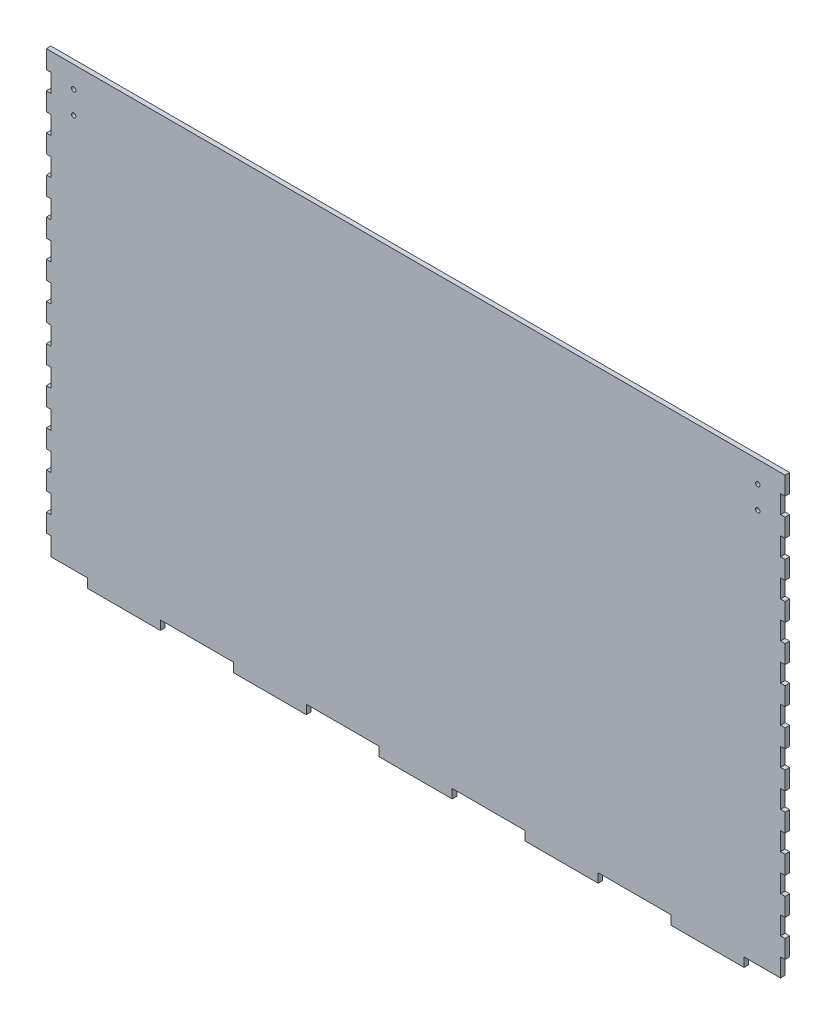
SolidWorks part; units mm, degrees
ref_plane "Front Plane" through (0, 0, 0) normal (0, 0, 1) x (1, 0, 0)
ref_plane "Top Plane" through (0, 0, 0) normal (0, 1, 0) x (1, 0, 0)
ref_plane "Right Plane" through (0, 0, 0) normal (1, 0, 0) x (0, 0, -1)
sketch "Sketch1" plane through (0, 0, 0) normal (0, 0, 1) x (1, 0, 0)
  line L0 (0, 0) -> (508, 0)
  line L1 (508, 0) -> (508, 304.8)
  line L2 (508, 304.8) -> (0, 304.8)
  line L3 (0, 304.8) -> (0, 0)
  line L4 (254, 304.8) -> (254, 0) construction
  line L5 (0, 304.8) -> (-3.175, 304.8)
  line L6 (-3.175, 304.8) -> (-3.175, 292.1)
  line L7 (-3.175, 292.1) -> (0, 292.1)
  line L8 (25.4, 0) -> (25.4, -6.35)
  line L9 (25.4, -6.35) -> (76.2, -6.35)
  line L10 (76.2, -6.35) -> (76.2, 0)
  line L13 (0, 279.4) -> (-3.175, 279.4)
  line L14 (-3.175, 279.4) -> (-3.175, 266.7)
  line L15 (-3.175, 266.7) -> (0, 266.7)
  line L17 (0, 254) -> (-3.175, 254)
  line L18 (-3.175, 254) -> (-3.175, 241.3)
  line L19 (-3.175, 241.3) -> (0, 241.3)
  line L21 (0, 228.6) -> (-3.175, 228.6)
  line L22 (-3.175, 228.6) -> (-3.175, 215.9)
  line L23 (-3.175, 215.9) -> (0, 215.9)
  line L25 (0, 203.2) -> (-3.175, 203.2)
  line L26 (-3.175, 203.2) -> (-3.175, 190.5)
  line L27 (-3.175, 190.5) -> (0, 190.5)
  line L29 (0, 177.8) -> (-3.175, 177.8)
  line L30 (-3.175, 177.8) -> (-3.175, 165.1)
  line L31 (-3.175, 165.1) -> (0, 165.1)
  line L33 (0, 152.4) -> (-3.175, 152.4)
  line L34 (-3.175, 152.4) -> (-3.175, 139.7)
  line L35 (-3.175, 139.7) -> (0, 139.7)
  line L37 (0, 127) -> (-3.175, 127)
  line L38 (-3.175, 127) -> (-3.175, 114.3)
  line L39 (-3.175, 114.3) -> (0, 114.3)
  line L41 (0, 101.6) -> (-3.175, 101.6)
  line L42 (-3.175, 101.6) -> (-3.175, 88.9)
  line L43 (-3.175, 88.9) -> (0, 88.9)
  line L45 (0, 76.2) -> (-3.175, 76.2)
  line L46 (-3.175, 76.2) -> (-3.175, 63.5)
  line L47 (-3.175, 63.5) -> (0, 63.5)
  line L49 (0, 50.8) -> (-3.175, 50.8)
  line L50 (-3.175, 50.8) -> (-3.175, 38.1)
  line L51 (-3.175, 38.1) -> (0, 38.1)
  line L53 (0, 25.4) -> (-3.175, 25.4)
  line L54 (-3.175, 25.4) -> (-3.175, 12.7)
  line L55 (-3.175, 12.7) -> (0, 12.7)
  line L57 (0, 304.8) -> (0, 279.4) construction
  line L59 (127, 0) -> (127, -6.35)
  line L60 (127, -6.35) -> (177.8, -6.35)
  line L61 (177.8, -6.35) -> (177.8, 0)
  line L63 (228.6, 0) -> (228.6, -6.35)
  line L64 (228.6, -6.35) -> (279.4, -6.35)
  line L65 (279.4, -6.35) -> (279.4, 0)
  line L67 (330.2, 0) -> (330.2, -6.35)
  line L68 (330.2, -6.35) -> (381, -6.35)
  line L69 (381, -6.35) -> (381, 0)
  line L70 (76.2, 0) -> (177.8, 0) construction
  line L72 (431.8, 0) -> (431.8, -6.35)
  line L73 (431.8, -6.35) -> (482.6, -6.35)
  line L74 (482.6, -6.35) -> (482.6, 0)
  line L76 (511.175, 12.7) -> (508, 12.7)
  line L77 (511.175, 25.4) -> (511.175, 12.7)
  line L78 (508, 25.4) -> (511.175, 25.4)
  line L80 (511.175, 38.1) -> (508, 38.1)
  line L81 (511.175, 50.8) -> (511.175, 38.1)
  line L82 (508, 50.8) -> (511.175, 50.8)
  line L84 (511.175, 63.5) -> (508, 63.5)
  line L85 (511.175, 76.2) -> (511.175, 63.5)
  line L86 (508, 76.2) -> (511.175, 76.2)
  line L88 (511.175, 88.9) -> (508, 88.9)
  line L89 (511.175, 101.6) -> (511.175, 88.9)
  line L90 (508, 101.6) -> (511.175, 101.6)
  line L92 (511.175, 114.3) -> (508, 114.3)
  line L93 (511.175, 127) -> (511.175, 114.3)
  line L94 (508, 127) -> (511.175, 127)
  line L96 (511.175, 139.7) -> (508, 139.7)
  line L97 (511.175, 152.4) -> (511.175, 139.7)
  line L98 (508, 152.4) -> (511.175, 152.4)
  line L100 (511.175, 165.1) -> (508, 165.1)
  line L101 (511.175, 177.8) -> (511.175, 165.1)
  line L102 (508, 177.8) -> (511.175, 177.8)
  line L104 (511.175, 190.5) -> (508, 190.5)
  line L105 (511.175, 203.2) -> (511.175, 190.5)
  line L106 (508, 203.2) -> (511.175, 203.2)
  line L108 (511.175, 215.9) -> (508, 215.9)
  line L109 (511.175, 228.6) -> (511.175, 215.9)
  line L110 (508, 228.6) -> (511.175, 228.6)
  line L112 (511.175, 241.3) -> (508, 241.3)
  line L113 (511.175, 254) -> (511.175, 241.3)
  line L114 (508, 254) -> (511.175, 254)
  line L116 (511.175, 266.7) -> (508, 266.7)
  line L117 (511.175, 279.4) -> (511.175, 266.7)
  line L118 (508, 279.4) -> (511.175, 279.4)
  line L120 (511.175, 292.1) -> (508, 292.1)
  line L121 (511.175, 304.8) -> (511.175, 292.1)
  line L122 (508, 304.8) -> (511.175, 304.8)
  dimension "D1" = 508
  dimension "D2" = 304.8
  dimension "D3" = 3.175
  dimension "D4" = 12.7
  dimension "D5" = 6.35
  dimension "D6" = 50.8
  dimension "D7" = 25.4
  dimension "D9" = 25.4
  dimension "D11" = 101.6
  dimension "D8" = 12
  dimension "D10" = 5
extrude "Boss-Extrude1" add sketch "Sketch1" along normal blind 3.175 contours L2 L3 L0 L1 | L9 L10 L0 L8 | L60 L61 L0 L59 | L64 L65 L0 L63 | L68 L69 L0 L67 | L73 L74 L0 L72 | L54 L55 L3 L53 | L50 L51 L3 L49 | L46 L47 L3 L45 | L42 L43 L3 L41 | L38 L39 L3 L37 | L34 L35 L3 L33 | L30 L31 L3 L29 | L26 L27 L3 L25 | L22 L23 L3 L21 | L18 L19 L3 L17 | L14 L15 L3 L13 | L6 L7 L3 L5 | L78 L1 L76 L77 | L82 L1 L80 L81 | L86 L1 L84 L85 | L90 L1 L88 L89 | L98 L1 L96 L97 | L94 L1 L92 L93 | L102 L1 L100 L101 | L106 L1 L104 L105 | L110 L1 L108 L109 | L114 L1 L112 L113 | L118 L1 L116 L117 | L122 L1 L120 L121 region at (254, 152.4, 0) region at (50.8, -3.175, 0) region at (-1.5875, 19.05, 0) region at (152.4, -3.175, 0) region at (-1.5875, 44.45, 0) region at (254, -3.175, 0) region at (-1.5875, 69.85, 0) region at (355.6, -3.175, 0) region at (-1.5875, 95.25, 0) region at (457.2, -3.175, 0) region at (-1.5875, 120.65, 0) region at (-1.5875, 146.05, 0) region at (509.5875, 19.05, 0) region at (-1.5875, 171.45, 0) region at (509.5875, 44.45, 0) region at (-1.5875, 196.85, 0) region at (509.5875, 69.85, 0) region at (-1.5875, 222.25, 0) region at (509.5875, 95.25, 0) region at (-1.5875, 247.65, 0) region at (509.5875, 120.65, 0) region at (-1.5875, 273.05, 0) region at (509.5875, 146.05, 0) region at (-1.5875, 298.45, 0) region at (509.5875, 171.45, 0) region at (509.5875, 298.45, 0) region at (509.5875, 196.85, 0) region at (509.5875, 273.05, 0) region at (509.5875, 222.25, 0) region at (509.5875, 247.65, 0)
sketch "Sketch2" plane through (0, 0, 3.175) normal (0, 0, 1) x (1, 0, 0)
  line L1 (511.175, 304.8) -> (-3.175, 304.8) construction
  line L2 (254, 304.8) -> (254, -6.35) construction
  line L3 (228.6, -6.35) -> (279.4, -6.35) construction
  line L4 (-3.175, 304.8) -> (-3.175, 292.1) construction
  circle A0 centre (15.875, 289.8) radius 1.5
  circle A1 centre (15.875, 274.05) radius 1.5
  circle A2 centre (492.125, 289.8) radius 1.5
  circle A3 centre (492.125, 274.05) radius 1.5
  dimension "D1" = 3
  dimension "D2" = 3
  dimension "D3" = 19.05
  dimension "D4" = 15.75
  dimension "D5" = 15
extrude "Cut-Extrude1" cut sketch "Sketch2" against normal up to surface (3.175 mm away) up to face at (254, 125.5767, 0)
equation "\"wall_thickness\"= 0.125in"
equation "\"base_thickness\"= 0.25in"
equation "\"D3@Sketch1\"=\"wall_thickness\""
equation "\"D5@Sketch1\"=\"base_thickness\""
equation "\"D1@Boss-Extrude1\"=\"wall_thickness\""
